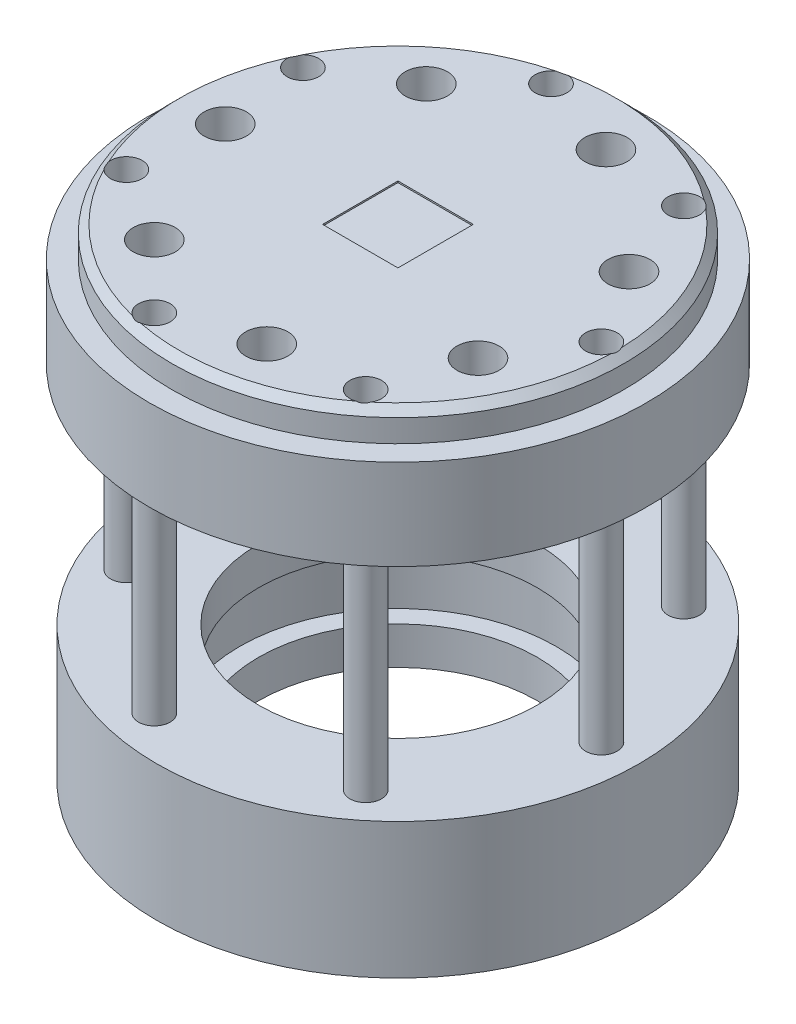
SolidWorks part; units mm, degrees
ref_plane "Front" through (0, 0, 0) normal (0, 0, 1) x (1, 0, 0)
ref_plane "Top" through (0, 0, 0) normal (0, 1, 0) x (1, 0, 0)
ref_plane "Right" through (0, 0, 0) normal (1, 0, 0) x (0, 0, -1)
sketch "Sketch1" plane through (0, 0, 0) normal (0, 1, 0) x (1, 0, 0)
  line L0 (14.55, 0) -> (16, 0) construction
  line L1 (12.45, 0) -> (10.5, 0) construction
  circle A0 centre (0, 0) radius 13.5 construction
  circle A1 centre (13.5, 0) radius 1.05 construction
  circle A2 centre (0, 0) radius 16
  circle A3 centre (0, 0) radius 10.5
  point P9 (12.45, 0)
  dimension "D1" = 2.1
  dimension "D2" = 27
  dimension "D3" = 32
  dimension "D4" = 21
extrude "Boss-Extrude1" add sketch "Sketch1" along normal blind 9
sketch "Sketch2" plane through (0, 9, 0) normal (0, 1, 0) x (1, 0, 0)
  circle A0 centre (0, 0) radius 13.5 construction
  circle A1 centre (13.5, 0) radius 1.05
  circle A2 centre (8.4171, -10.5547) radius 1.05
  circle A3 centre (-3.004, -13.1615) radius 1.05
  circle A4 centre (-12.1631, -5.8574) radius 1.05
  circle A5 centre (-12.1631, 5.8574) radius 1.05
  circle A6 centre (-3.004, 13.1615) radius 1.05
  circle A7 centre (8.4171, 10.5547) radius 1.05
  dimension "D1" = 27
  dimension "D2" = 2.1
  dimension "D3" = 7
extrude "Boss-Extrude2" add sketch "Sketch2" along normal blind 15
sketch "Sketch3" plane through (0, 9, 0) normal (0, 1, 0) x (1, 0, 0)
  circle A0 centre (0, 0) radius 9.25
  circle A1 centre (0, 0) radius 10.5 construction
  circle A2 centre (0, 0) radius 10.5
  dimension "D1" = 18.5
extrude "Boss-Extrude3" add sketch "Sketch3" against normal blind 2.5
extrude "Boss-Extrude4" add sketch "Sketch3<3>" along normal blind 2.5 from surface starting at face at (0, 0, 16)
sketch "Sketch3<3>" plane through (0, 9, 0) normal (0, 1, 0) x (1, 0, 0) same geometry as "Sketch3"
sketch "Sketch4" plane through (0, 24, 0) normal (0, 1, 0) x (1, 0, 0)
  circle A0 centre (0, 0) radius 16.5
  dimension "D1" = 33
extrude "Boss-Extrude5" add sketch "Sketch4" along normal blind 6
sketch "Sketch6" plane through (0, 30, 0) normal (0, 1, 0) x (1, 0, 0)
  circle A0 centre (0, 0) radius 15
  dimension "D1" = 30
extrude "Boss-Extrude6" add sketch "Sketch6" along normal blind 2
sketch "Sketch8" plane through (0, 24, 0) normal (0, -1, 0) x (1, 0, 0)
  circle A0 centre (0, 0) radius 7.5
  dimension "D1" = 15
extrude "Cut-Extrude1" cut sketch "Sketch8" against normal blind 4
chamfer "Chamfer1" distance 0.5 angle 45 1 edges at (0, 24, -7.5)
sketch "Sketch9" plane through (0, 28, 0) normal (0, -1, 0) x (1, 0, 0)
  circle A0 centre (0, 0) radius 6
  dimension "D1" = 12
extrude "Cut-Extrude2" cut sketch "Sketch9" against normal blind 1.5
chamfer "Chamfer2" distance 0.5 angle 45 1 edges at (0, 32, 15)
sketch "Sketch10" plane through (0, 9, 0) normal (0, 1, 0) x (1, 0, 0)
  circle A1 centre (8.4171, -10.5547) radius 1.05
  circle A2 centre (8.4171, -10.5547) radius 1.05
  circle A3 centre (13.5, 0) radius 1.05
  circle A4 centre (13.5, 0) radius 1.05
  circle A7 centre (8.4171, 10.5547) radius 1.05
  circle A8 centre (8.4171, 10.5547) radius 1.05
  circle A9 centre (-3.004, 13.1615) radius 1.05
  circle A10 centre (-3.004, 13.1615) radius 1.05
  circle A11 centre (-12.1631, 5.8574) radius 1.05
  circle A12 centre (-12.1631, 5.8574) radius 1.05
  circle A13 centre (-12.1631, -5.8574) radius 1.05
  circle A14 centre (-12.1631, -5.8574) radius 1.05
  circle A15 centre (-3.004, -13.1615) radius 1.05
  circle A16 centre (-3.004, -13.1615) radius 1.05
  dimension "D1" = 0
  dimension "D2" = 0
  dimension "D4" = 0
  dimension "D5" = 0
  dimension "D6" = 0
  dimension "D7" = 0
  dimension "D8" = 0
extrude "Cut-Extrude3" cut sketch "Sketch10" against normal blind 7
sketch "Sketch11" plane through (0, 24, 0) normal (0, -1, 0) x (1, 0, 0)
  circle A1 centre (8.4171, -10.5547) radius 1.05
  circle A3 centre (8.4171, -10.5547) radius 1.05
  circle A4 centre (-3.004, -13.1615) radius 1.05
  circle A5 centre (-3.004, -13.1615) radius 1.05
  circle A6 centre (-12.1631, -5.8574) radius 1.05
  circle A7 centre (-12.1631, -5.8574) radius 1.05
  circle A8 centre (-12.1631, 5.8574) radius 1.05
  circle A9 centre (-12.1631, 5.8574) radius 1.05
  circle A10 centre (-3.004, 13.1615) radius 1.05
  circle A11 centre (-3.004, 13.1615) radius 1.05
  circle A12 centre (8.4171, 10.5547) radius 1.05
  circle A13 centre (8.4171, 10.5547) radius 1.05
  circle A14 centre (13.5, 0) radius 1.05
  circle A15 centre (13.5, 0) radius 1.05
  dimension "D1" = 0
  dimension "D2" = 0
  dimension "D3" = 0
  dimension "D4" = 0
  dimension "D5" = 0
  dimension "D6" = 0
  dimension "D7" = 0
extrude "Cut-Extrude4" cut sketch "Sketch11" against normal up to surface (8 mm away) up to face at (0, 32, 14.5)
sketch "Sketch12" plane through (0, 24, 0) normal (0, 1, 0) x (1, 0, 0)
  line L0 (0, 0) -> (10.3797, 4.9509) construction
  circle A1 centre (10.3797, 4.9509) radius 3
  circle A2 centre (0, 0) radius 8 construction
  circle A3 centre (0, 0) radius 8 construction
  circle A4 centre (10.3797, 4.9509) radius 1.4 construction
  dimension "D2" = 6
  dimension "D3" = 2.8
  dimension "D1" = 11.5
  dimension "D4" = 25.5
extrude "Cut-Extrude5" cut sketch "Sketch12" along normal blind 5
sketch "Sketch13" plane through (0, 29, 0) normal (0, -1, 0) x (1, 0, 0)
  circle A0 centre (10.3797, -4.9509) radius 1.4
  dimension "D1" = 2.8
extrude "Cut-Extrude6" cut sketch "Sketch13" against normal up to surface (3 mm away) up to face at (0, 32, 0)
pattern_circular "CirPattern1" count 7 over 360 about axis through (0, 30, 0) along (0, 1, 0) of "Cut-Extrude5", "Cut-Extrude6"
chamfer "Chamfer3" distance 0.5 angle 45 7 edges at (-4.2117, 24, -9.6854) (4.9464, 24, -9.3316) (-10.1983, 24, -2.7459) (-8.5054, 24, 6.2613) (-0.4077, 24, 10.5536) (10.3797, 24, -1.9509) (7.9969, 24, 6.8988)
sketch "Sketch14" plane through (0, 32, 0) normal (0, 1, 0) x (1, 0, 0)
  line L1 (-2.5, -2.5) -> (2.5, -2.5)
  line L2 (-2.5, -2.5) -> (-2.5, 2.5)
  line L3 (-2.5, 2.5) -> (2.5, 2.5)
  line L4 (2.5, -2.5) -> (2.5, 2.5)
  line L5 (-2.5, -2.5) -> (2.5, 2.5) construction
  line L6 (-2.5, 2.5) -> (2.5, -2.5) construction
  point P0 (0, 0)
  dimension "D1" = 5
extrude "Cut-Extrude7" cut sketch "Sketch14" against normal blind 0.1
